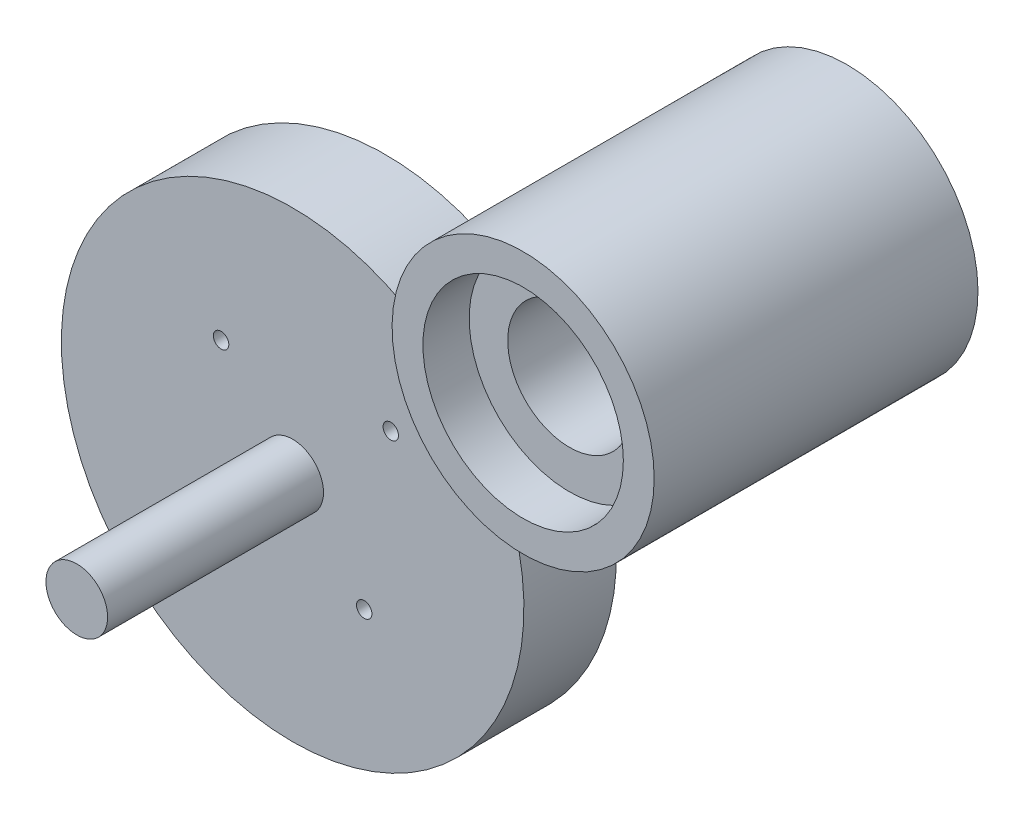
SolidWorks part; units mm, degrees
note: The reader was unsure of these and kept them because the rebuilt part matched: shared geometry of "Sketch2<14>", "Sketch2<7>", "Sketch2<16>".
ref_plane "Front Plane" through (0, 0, 0) normal (0, 0, 1) x (1, 0, 0)
ref_plane "Top Plane" through (0, 0, 0) normal (0, 1, 0) x (1, 0, 0)
ref_plane "Right Plane" through (0, 0, 0) normal (1, 0, 0) x (0, 0, -1)
sketch "Sketch2" plane through (0, 0, 0) normal (0, 0, 1) x (1, 0, 0)
  line L0 (26.3143, 34.5802) -> (-3.6335, 8.0635) construction
  line L1 (-13.5772, 19.2939) -> (6.3103, -3.1669) construction
  line L2 (17.8533, 33.7669) -> (3.6401, 21.1821)
  line L3 (21.1678, 30.0234) -> (24.4824, 26.2799) construction
  line L4 (21.1678, 30.0234) -> (17.8533, 33.7669) construction
  line L5 (24.4824, 26.2799) -> (10.2692, 13.6951)
  line L6 (3.6401, 21.1821) -> (10.2692, 13.6951) construction
  circle A0 centre (26.3143, 34.5802) radius 2
  circle A1 centre (26.3143, 34.5802) radius 8.5
  circle A4 centre (26.3143, 34.5802) radius 4
  circle A5 centre (26.3143, 34.5802) radius 6.5
  circle A6 centre (-3.6335, 8.0635) radius 15
  circle A7 centre (-8.2739, 13.3044) radius 0.5
  circle A8 centre (2.7304, 13.6983) radius 0.5
  circle A9 centre (1.0069, 2.8227) radius 0.5
  circle A10 centre (-9.9974, 2.4287) radius 0.5
  circle A11 centre (-3.6335, 8.0635) radius 2
  arc A13 (90.1971, 16.0576) -> (88.4187, 27.9251) centre (95.2623, 22.8836) ccw construction
  circle A14 centre (125.21, 49.4003) radius 4 construction
  circle A15 centre (125.21, 49.4003) radius 6.5 construction
  point P6 (6.9546, 17.4386)
  point P12 (21.1678, 30.0234)
  dimension "D2" = 4
  dimension "D1" = 30
  dimension "D10" = 1
  dimension "D11" = 4
  dimension "D4" = 10
  dimension "D7" = 8.5
  dimension "D9" = 7
extrude "Boss-Extrude2" add sketch "Sketch2" along normal blind 6
extrude "Boss-Extrude9" add sketch "Sketch2<14>" along normal blind 20 contours A11
sketch "Sketch2<14>" plane through (0, 0, 0) normal (0, 0, 1) x (1, 0, 0) same geometry as "Sketch2"
extrude "Boss-Extrude5" add sketch "Sketch2<7>" along normal offset from surface (15 mm away) 1 from surface at 6 contours A1 A4
sketch "Sketch2<7>" plane through (0, 0, 0) normal (0, 0, 1) x (1, 0, 0) same geometry as "Sketch2"
extrude "Boss-Extrude10" add sketch "Sketch2<16>" along normal offset from surface (15 mm away) 3 from offset 3 contours A5 A4 up to face at (32.8143, 34.5802, 21)
sketch "Sketch2<16>" plane through (0, 0, 0) normal (0, 0, 1) x (1, 0, 0) same geometry as "Sketch2"
ref_plane "Plane2" through (-5.5989, 6.3233, 0) normal (0.6629, -0.7487, 0) x (-0.7487, -0.6629, 0)
sketch "Sketch6" plane through (-5.5989, 6.3233, 0) normal (-0.6629, 0.7487, 0) x (0.7487, 0.6629, 0)
  line L0 (34.1251, -13.5) -> (23.7512, -6)
  line L6 (34.1251, -6) -> (34.1251, -21) construction
  line L7 (35.7512, -6) -> (16.7672, -6) construction
  dimension "D1" = 12
rib "Rib20" sketch "Sketch6" sketch "Sketch6" thickness 10 extrusion direction parallel to sketch draft on no parameters "D1"=10
